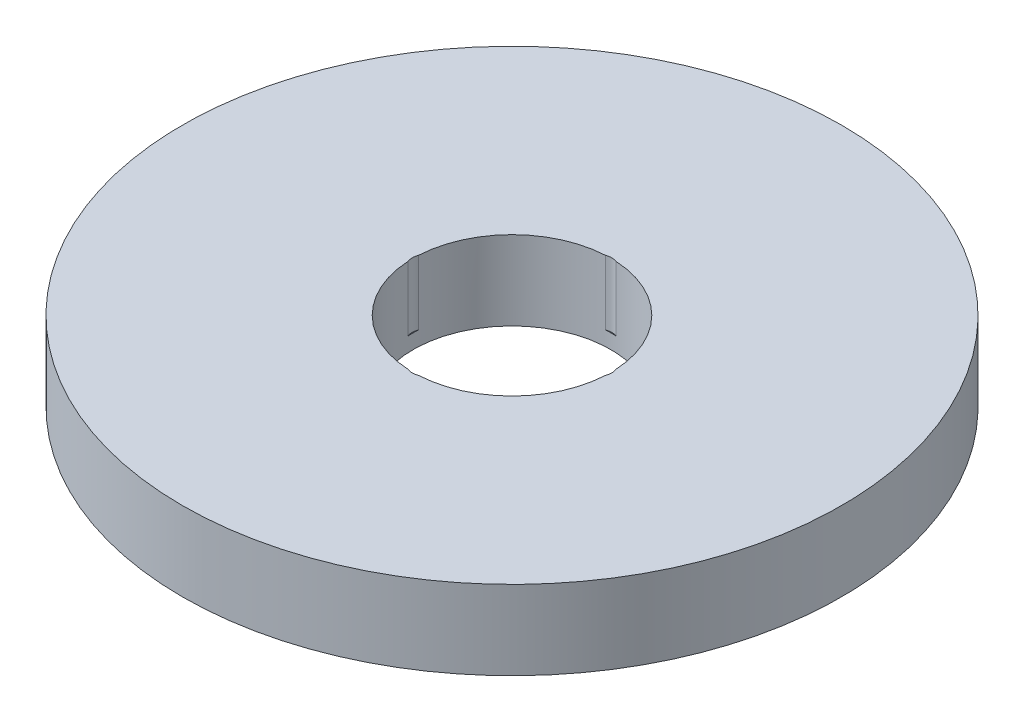
SolidWorks part; units mm, degrees
ref_plane "Front Plane" through (0, 0, 0) normal (0, 0, 1) x (1, 0, 0)
ref_plane "Top Plane" through (0, 0, 0) normal (0, 1, 0) x (1, 0, 0)
ref_plane "Right Plane" through (0, 0, 0) normal (1, 0, 0) x (0, 0, -1)
sketch "Sketch1" plane through (0, 0, 0) normal (0, 1, 0) x (1, 0, 0)
  circle A0 centre (0, 0) radius 50
  dimension "FLANGE_OD" = 100
extrude "Boss-Extrude1" add sketch "Sketch1" along normal blind 12
sketch "Sketch2" plane through (0, 0, 0) normal (0, 1, 0) x (1, 0, 0)
  circle A0 centre (0, 0) radius 15
  dimension "BORE_D" = 30
extrude "Cut-Extrude1" cut sketch "Sketch2" along normal through all
sketch "Sketch3" plane through (0, 12, 0) normal (0, 1, 0) x (1, 0, 0)
  circle A0 centre (0, 0) radius 13.0241 construction
  circle A1 centre (-13.0241, 0) radius 2.106
  dimension "BOLT_D" = 4.212
  dimension "BOLT_PCD" = 26.0483
extrude "Cut-Extrude2" cut sketch "Sketch3" against normal blind 9.799
pattern_circular "CirPattern1" count 4 over 360 about axis through (0, 0, 0) along (0, 1, 0) of "Cut-Extrude2"
